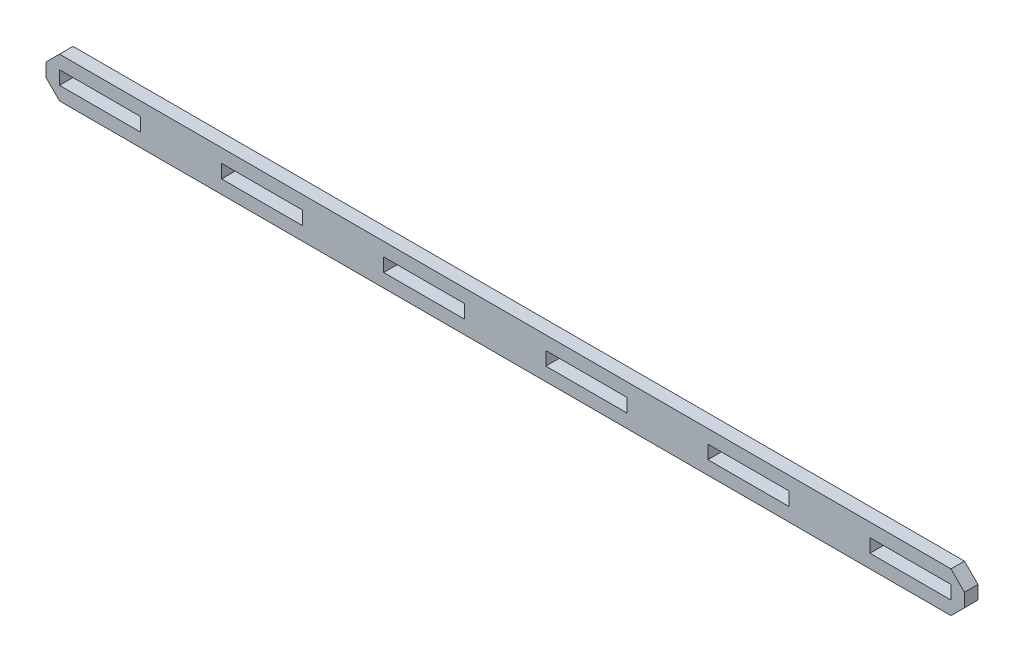
SolidWorks part; units mm, degrees
ref_plane "Front Plane" through (0, 0, 0) normal (0, 0, 1) x (1, 0, 0)
ref_plane "Top Plane" through (0, 0, 0) normal (0, 1, 0) x (1, 0, 0)
ref_plane "Right Plane" through (0, 0, 0) normal (1, 0, 0) x (0, 0, -1)
sketch "Sketch2" plane through (0, 0, 0) normal (0, 0, 1) x (1, 0, 0)
  line L0 (-62.0408, 2.298) -> (293.3705, 2.298) construction
  line L1 (-57.0408, 9.798) -> (272.9592, 9.798)
  line L2 (-62.0408, 4.798) -> (-62.0408, -0.202)
  line L3 (-57.0408, -5.202) -> (272.9592, -5.202)
  line L4 (277.9592, 4.798) -> (277.9592, -0.202)
  line L5 (107.9592, 9.798) -> (107.9592, -14.6506) construction
  line L6 (2.9592, 4.798) -> (2.9592, -0.202)
  line L7 (62.9592, 4.798) -> (92.9592, 4.798)
  line L8 (62.9592, 4.798) -> (62.9592, -0.202)
  line L9 (62.9592, -0.202) -> (92.9592, -0.202)
  line L10 (92.9592, 4.798) -> (92.9592, -0.202)
  line L11 (2.9592, 4.798) -> (32.9592, 4.798)
  line L12 (32.9592, 4.798) -> (32.9592, -0.202)
  line L13 (2.9592, -0.202) -> (32.9592, -0.202)
  line L14 (-57.0408, 4.798) -> (-57.0408, -0.202)
  line L15 (-57.0408, 4.798) -> (-27.0408, 4.798)
  line L16 (-27.0408, 4.798) -> (-27.0408, -0.202)
  line L17 (-57.0408, -0.202) -> (-27.0408, -0.202)
  line L18 (272.9592, 4.798) -> (242.9592, 4.798)
  line L19 (242.9592, 4.798) -> (242.9592, -0.202)
  line L20 (272.9592, -0.202) -> (242.9592, -0.202)
  line L21 (272.9592, 4.798) -> (272.9592, -0.202)
  line L22 (212.9592, 4.798) -> (182.9592, 4.798)
  line L23 (182.9592, 4.798) -> (182.9592, -0.202)
  line L24 (212.9592, -0.202) -> (182.9592, -0.202)
  line L25 (212.9592, 4.798) -> (212.9592, -0.202)
  line L26 (152.9592, -0.202) -> (122.9592, -0.202)
  line L27 (122.9592, 4.798) -> (122.9592, -0.202)
  line L28 (152.9592, 4.798) -> (122.9592, 4.798)
  line L29 (152.9592, 4.798) -> (152.9592, -0.202)
  line L30 (-62.0408, 4.798) -> (-57.0408, 9.798)
  line L31 (-62.0408, -0.202) -> (-57.0408, -5.202)
  line L32 (272.9592, 9.798) -> (277.9592, 4.798)
  line L33 (277.9592, -0.202) -> (272.9592, -5.202)
  point P0 (-62.0408, 9.798)
  point P1 (277.9592, -5.202)
  point P2 (-62.0408, -5.202)
  point P3 (277.9592, 9.798)
  dimension "D1" = 15
  dimension "D2" = 340
  dimension "D3" = 5
  dimension "D4" = 30
  dimension "D5" = 15
  dimension "D6" = 2.5
  dimension "D7" = 3
extrude "Boss-Extrude1" add sketch "Sketch2" along normal blind 5
